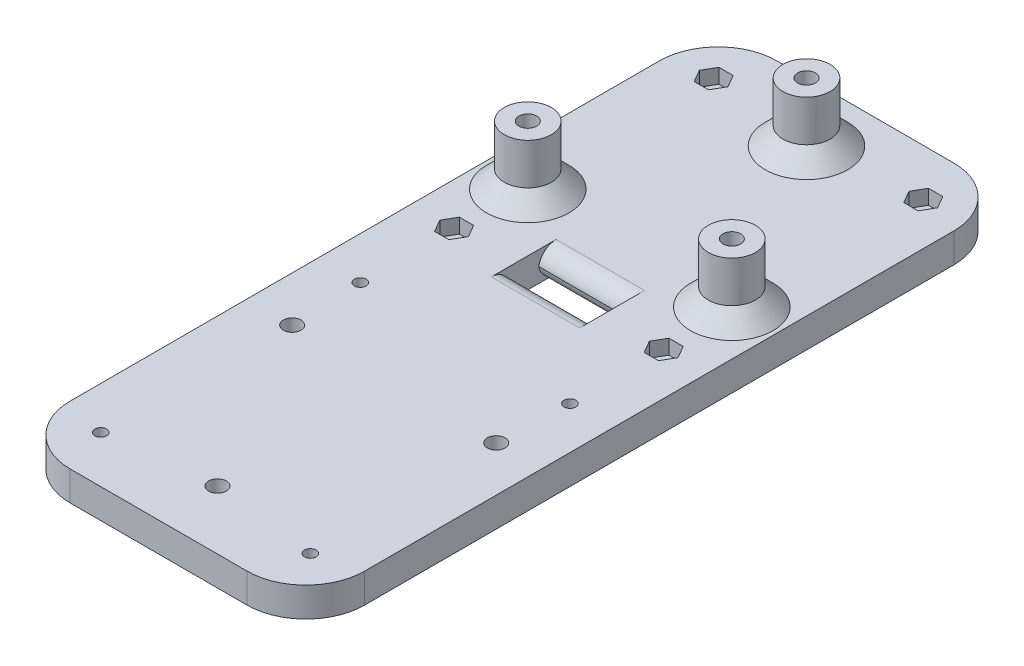
SolidWorks part; units mm, degrees
ref_plane "前视基准面" through (0, 0, 0) normal (0, 0, 1) x (1, 0, 0)
ref_plane "上视基准面" through (0, 0, 0) normal (0, 1, 0) x (1, 0, 0)
ref_plane "右视基准面" through (0, 0, 0) normal (1, 0, 0) x (0, 0, -1)
sketch "草图1" plane through (0, 0, 0) normal (0, 1, 0) x (1, 0, 0)
  line L0 (-25, 0) -> (25, 0) construction
  line L1 (-25, 30) -> (25, 30)
  line L2 (-25, 30) -> (-25, -30)
  line L3 (-25, -30) -> (25, -30)
  line L4 (25, 30) -> (25, -30)
  line L5 (-25, 30) -> (25, -30) construction
  line L6 (-25, -30) -> (25, 30) construction
  line L7 (0, 30) -> (0, -30) construction
  line L8 (0, 0) -> (-17.3205, -10) construction
  line L9 (0, 0) -> (0, 20) construction
  line L10 (0, 0) -> (17.3205, -10) construction
  circle A0 centre (-17.7955, 22.0345) radius 1
  circle A1 centre (17.7955, 22.0345) radius 1
  circle A2 centre (17.7955, -22.0345) radius 1
  circle A3 centre (-17.7955, -22.0345) radius 1
  circle A8 centre (0, 0) radius 20 construction
  circle A9 centre (-17.3205, -10) radius 1.5
  circle A10 centre (17.3205, -10) radius 1.5
  circle A11 centre (0, 20) radius 1.5
  point P0 (0, 0)
  dimension "D4" = 2
  dimension "D5" = 2
  dimension "D14" = 40
  dimension "D15" = 3
  dimension "D16" = 3
  dimension "D17" = 3
  dimension "D1" = 60
  dimension "D2" = 50
  dimension "D3" = 35.591
  dimension "D6" = 7.2045
  dimension "D7" = 7.9655
extrude "凸台-拉伸1" add sketch "草图1" along normal blind 5
fillet "圆角1" radius 10 2 edges at (-25, 2.5, -30) (25, 2.5, -30)
sketch "草图5" plane through (0, 5, 0) normal (0, 1, 0) x (1, 0, 0)
  circle A1 centre (-17.3205, -10) radius 4
  circle A2 centre (17.3205, -10) radius 4
  circle A3 centre (0, 20) radius 4
  circle A4 centre (-17.3205, -10) radius 1.5
  circle A5 centre (17.3205, -10) radius 1.5
  circle A6 centre (0, 20) radius 1.5
  dimension "D1" = 8
  dimension "D2" = 8
  dimension "D3" = 8
extrude "凸台-拉伸3" add sketch "草图5" along normal blind 10
sketch "草图6" plane through (0, 0, 0) normal (0, -1, 0) x (1, 0, 0)
  circle A0 centre (-17.3205, 10) radius 3
  circle A1 centre (17.3205, 10) radius 3
  circle A2 centre (0, -20) radius 3
  dimension "D1" = 6
  dimension "D2" = 6
  dimension "D3" = 6
extrude "切除-拉伸1" cut sketch "草图6" against normal blind 2
fillet "圆角2" radius 2 3 edges at (-17.3205, 0, 7) (17.3205, 0, 7) (0, 0, -23)
sketch "草图7" plane through (0, 5, 0) normal (0, 1, 0) x (1, 0, 0)
  line L0 (0, 0) -> (0, -30) construction
  line L1 (-25, -30) -> (25, -30) construction
  line L3 (0, 0) -> (0, -18) construction
  line L4 (-7.5, -18) -> (7.5, -18)
  line L5 (-7.5, -18) -> (-7.5, -23)
  line L6 (-7.5, -23) -> (7.5, -23)
  line L7 (7.5, -18) -> (7.5, -23)
  line L8 (-7.5, -18) -> (7.5, -23) construction
  line L9 (-7.5, -23) -> (7.5, -18) construction
  point P9 (0, -20.5)
  dimension "D1" = 5
  dimension "D2" = 15
  dimension "D3" = 18
extrude "切除-拉伸2" cut sketch "草图7" against normal through all
sketch "草图9" plane through (0, 5, 0) normal (0, 1, 0) x (1, 0, 0)
  line L1 (-15.3706, 22.0345) -> (-16.5831, 24.1345)
  line L2 (-16.5831, 24.1345) -> (-19.0079, 24.1345)
  line L3 (-19.0079, 24.1345) -> (-20.2204, 22.0345)
  line L4 (-20.2204, 22.0345) -> (-19.0079, 19.9345)
  line L5 (-19.0079, 19.9345) -> (-16.5831, 19.9345)
  line L6 (-16.5831, 19.9345) -> (-15.3706, 22.0345)
  line L7 (20.2204, 22.0345) -> (19.0079, 24.1345)
  line L8 (19.0079, 24.1345) -> (16.5831, 24.1345)
  line L9 (16.5831, 24.1345) -> (15.3706, 22.0345)
  line L10 (15.3706, 22.0345) -> (16.5831, 19.9345)
  line L11 (16.5831, 19.9345) -> (19.0079, 19.9345)
  line L12 (19.0079, 19.9345) -> (20.2204, 22.0345)
  line L13 (20.2204, -22.0345) -> (19.0079, -19.9345)
  line L14 (19.0079, -19.9345) -> (16.5831, -19.9345)
  line L15 (16.5831, -19.9345) -> (15.3706, -22.0345)
  line L16 (15.3706, -22.0345) -> (16.5831, -24.1345)
  line L17 (16.5831, -24.1345) -> (19.0079, -24.1345)
  line L18 (19.0079, -24.1345) -> (20.2204, -22.0345)
  line L19 (-15.3706, -22.0345) -> (-16.5831, -19.9345)
  line L20 (-16.5831, -19.9345) -> (-19.0079, -19.9345)
  line L21 (-19.0079, -19.9345) -> (-20.2204, -22.0345)
  line L22 (-20.2204, -22.0345) -> (-19.0079, -24.1345)
  line L23 (-19.0079, -24.1345) -> (-16.5831, -24.1345)
  line L24 (-16.5831, -24.1345) -> (-15.3706, -22.0345)
  circle A0 centre (-17.7955, 22.0345) radius 2.1 construction
  circle A1 centre (17.7955, 22.0345) radius 2.1 construction
  circle A2 centre (17.7955, -22.0345) radius 2.1 construction
  circle A3 centre (-17.7955, -22.0345) radius 2.1 construction
  point P28 (-17.7955, -19.9345)
  dimension "D1" = 4.2
  dimension "D2" = 4.2
  dimension "D3" = 4.2
  dimension "D4" = 4.2
extrude "切除-拉伸3" cut sketch "草图9" against normal blind 2.5
chamfer "倒角1" distance 3 angle 45 3 edges at (0, 5, -16) (17.3205, 5, 14) (-17.3205, 5, 14)
fillet "圆角5" radius 3 4 edges at (0, 0, 18) (0, 0, 23) (0, 5, 23) (0, 5, 18)
mirror "镜向3" about plane through (-25, 5, 30) normal (0, 0, -1) of "凸台-拉伸1"
fillet "圆角6" radius 10 2 edges at (25, 2.5, 90) (-25, 2.5, 90)
